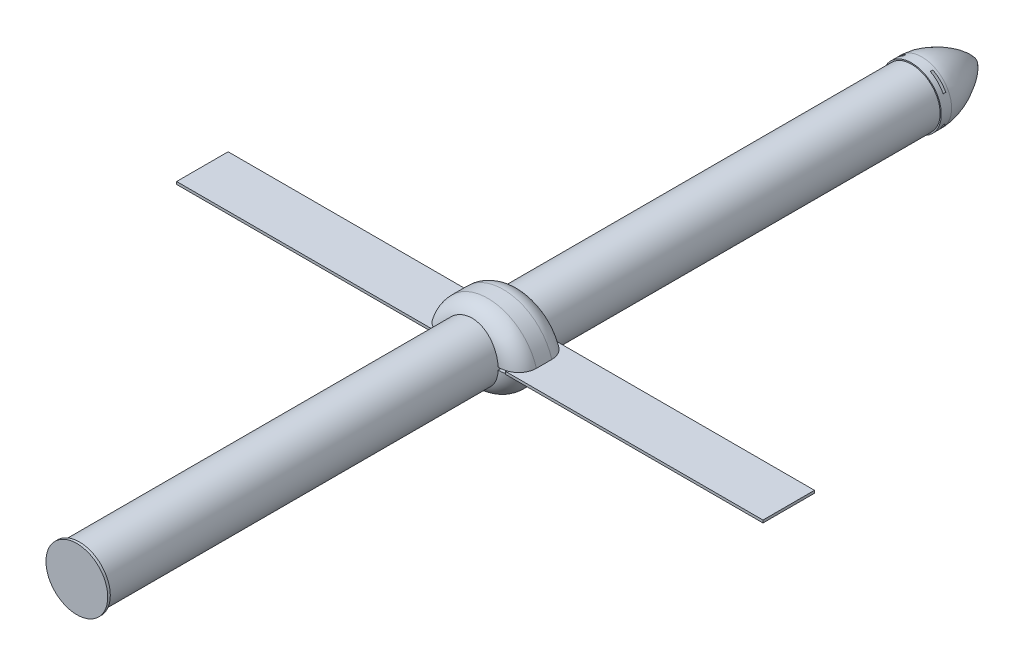
SolidWorks part; units mm, degrees
ref_plane "Front Plane" through (0, 0, 0) normal (0, 0, 1) x (1, 0, 0)
ref_plane "Top Plane" through (0, 0, 0) normal (0, 1, 0) x (1, 0, 0)
ref_plane "Right Plane" through (0, 0, 0) normal (1, 0, 0) x (0, 0, -1)
ref_plane "Plane1" through (0, 0, 10) normal (0, 0, 1) x (1, 0, 0)
sketch "Sketch1" plane through (0, 0, 10) normal (0, 0, 1) x (1, 0, 0)
  circle A0 centre (0, 0) radius 55.2
  dimension "D1" = 110.4
extrude "Boss-Extrude1" add sketch "Sketch1" along normal blind 798
sketch "Sketch3" plane through (0, 0, 808) normal (0, 0, 1) x (1, 0, 0)
  circle A0 centre (0, 0) radius 60
  dimension "D1" = 120
extrude "Boss-Extrude2" add sketch "Sketch3" along normal blind 5 contours A0
sketch "Sketch4" plane through (0, 0, 10) normal (0, 0, -1) x (-1, 0, 0)
  circle A0 centre (0, 0) radius 55.2
  dimension "D1" = 110.4
extrude "Boss-Extrude3" add sketch "Sketch4" along normal blind 20
sketch "Sketch5" plane through (0, 0, -10) normal (0, 0, -1) x (-1, 0, 0)
  circle A0 centre (0, 0) radius 55.2
  dimension "D1" = 110.4
extrude "Boss-Extrude4" add sketch "Sketch5" along normal blind 798
sketch "Sketch6" plane through (0, 0, -808) normal (0, 0, -1) x (-1, 0, 0)
  circle A0 centre (0, 0) radius 57.5
  dimension "D1" = 115
extrude "Boss-Extrude5" add sketch "Sketch6" along normal blind 10
sketch "Sketch7" plane through (0, 0, -818) normal (0, 0, -1) x (-1, 0, 0)
  line L0 (0, 25) -> (26.1895, 51.1895)
  line L1 (0, 25) -> (-26.1895, 51.1895)
  line L2 (-26.1895, 51.1895) -> (26.1895, 51.1895) construction
  circle A0 centre (0, 0) radius 57.5 construction
  arc A1 (-26.1895, 51.1895) -> (26.1895, 51.1895) centre (0, 0) cw
  circle M4 centre (0, 0) radius 57.5
  dimension "D1" = 25
  dimension "D2" = 90
extrude "Boss-Extrude6" add sketch "Sketch7" along normal blind 5 contours L2 M4 | L2 L1 L0 region at (0, 42.4596, -818) region at (0, 53.7259, -818)
pattern_circular "CirPattern1" count 4 over 360 about axis through (0, 0, -818) along (0, 0, -1) of "Boss-Extrude6"
sketch "Sketch8" plane through (0, 0, -823) normal (0, 0, -1) x (-1, 0, 0)
  circle A0 centre (0, 0) radius 57.5
  dimension "D1" = 115
extrude "Boss-Extrude7" add sketch "Sketch8" along normal blind 5
sketch "Sketch9" plane through (0, 0, 0) normal (0, 1, 0) x (1, 0, 0)
  line L0 (0, 828) -> (57.5, 828)
  line L2 (0, 931.7418) -> (0, 828)
  line L3 (57.5, 850.6026) -> (44.3947, 894.9386) construction
  line L4 (57.5, 828) -> (-57.5, 828) construction
  line L5 (44.3947, 894.9386) -> (11.0902, 931.7418) construction
  line L6 (57.5, 808) -> (57.5, 828) construction
  line L8 (57.5, 828) -> (57.5, 850.6026) construction
  line L9 (57.5, 850.6026) -> (44.3947, 894.9386) construction
  line L10 (44.3947, 894.9386) -> (11.0902, 931.7418) construction
  line L11 (11.0902, 931.7418) -> (0, 931.7418) construction
  spline S0 degree 4 poles (57.5, 828) (57.5, 850.6026) (44.3947, 894.9386) (11.0902, 931.7418) (0, 931.7418) knots 0 0 0 0 0 1 1 1 1 1
  dimension "D1" = 57.5
  dimension "D3" = 0
  dimension "D4" = 0
revolve "Revolve1" add sketch "Sketch9" angle 360 about L2
sketch "Sketch10" plane through (0, 0, 0) normal (0, 0, 1) x (1, 0, 0)
  line L0 (-94.2708, 2.5) -> (-55.1434, 2.5)
  line L1 (55.1434, 2.5) -> (94.2708, 2.5)
  arc A0 (94.2708, 2.5) -> (-94.2708, 2.5) centre (0, -25) ccw
  arc A1 (55.1434, 2.5) -> (-55.1434, 2.5) centre (0, 0) ccw
  point P2 (0, 55.2)
  point P3 (0, -25)
  point P8 (0, 73.2)
  dimension "D1" = 55.2
  dimension "D2" = 18
  dimension "D3" = 0
  dimension "D4" = 25
  dimension "D5" = 2.5
extrude "Boss-Extrude8" add sketch "Sketch10" along normal mid plane 100
fillet "Fillet1" radius 35 1 edges at (0, 73.2, 50) type face fillet first side face at (0, 33.35, 50) second side face at (0, 37.85, 0)
fillet "Fillet2" radius 35 1 edges at (0, 73.2, -50) type face fillet first side face at (0, 33.35, -50) second side face at (0, 37.85, -17.5)
mirror "Mirror2" about plane through (0, 0, 0) normal (0, 1, 0) of "Fillet1", "Fillet2", "Boss-Extrude8"
ref_plane "Plane2" through (-94.2708, 0, 0) normal (-1, 0, 0) x (0, 0, 1)
ref_plane "Plane3" through (-69.2708, 0, 0) normal (-1, 0, 0) x (0, 0, 1)
sketch "Sketch11" plane through (-69.2708, 0, 0) normal (-1, 0, 0) x (0, 0, 1)
  line L1 (-50, 2.5) -> (50, 2.5)
  line L2 (-50, 2.5) -> (-50, -2.5)
  line L3 (-50, -2.5) -> (50, -2.5)
  line L4 (50, 2.5) -> (50, -2.5)
extrude "Boss-Extrude9" add sketch "Sketch11" along normal blind 500
mirror "Mirror3" about plane through (0, 0, 0) normal (1, 0, 0) of "Boss-Extrude9"
